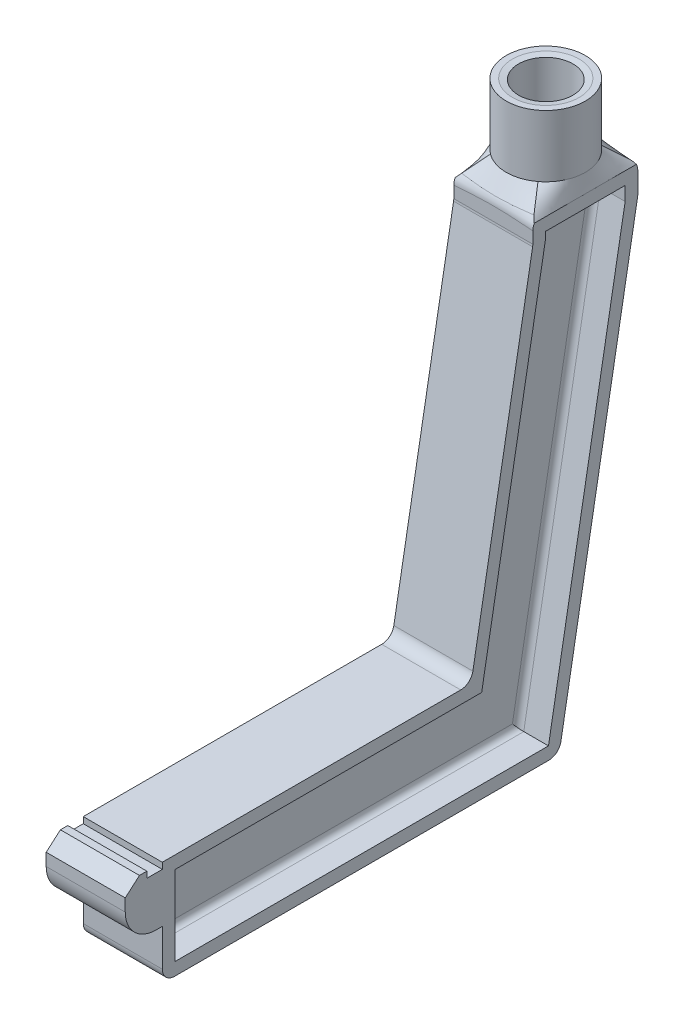
SolidWorks part; units mm, degrees
ref_plane "Front" through (0, 0, 0) normal (0, 0, 1) x (1, 0, 0)
ref_plane "Top" through (0, 0, 0) normal (0, 1, 0) x (1, 0, 0)
ref_plane "Right" through (0, 0, 0) normal (1, 0, 0) x (0, 0, -1)
sketch "Sketch1" plane through (0, 0, 0) normal (0, 1, 0) x (1, 0, 0)
  circle A0 centre (0, 0) radius 4.25 construction
  circle A1 centre (0, 0) radius 4.4
  circle A2 centre (0, 0) radius 6.4
  dimension "D1" = 8.5
  dimension "D3" = 2
  dimension "D2" = 0.15
extrude "Boss-Extrude1" add sketch "Sketch1" along normal blind 10
ref_plane "Plane1" through (0, -3, 0) normal (0, -1, 0) x (-1, 0, 0)
chamfer "Chamfer1" distance 1 angle 10 1 edges at (0, 10, 4.4) first distance on face at (0, 10, 6.4)
sketch "Sketch2" plane through (0, 0, 0) normal (0, -1, 0) x (1, 0, 0)
  circle A0 centre (0, 0) radius 6.4
  circle A1 centre (0, 0) radius 6.4 construction
sketch "Sketch3" plane through (0, -3, 0) normal (0, -1, 0) x (-1, 0, 0)
  line L1 (6.4, 8.5) -> (-6.4, 8.5)
  line L2 (6.4, 8.5) -> (6.4, -8.5)
  line L3 (6.4, -8.5) -> (-6.4, -8.5)
  line L4 (-6.4, 8.5) -> (-6.4, -8.5)
  line L5 (0, -8.5) -> (0, 8.5) construction
  line L6 (6.4, 0) -> (-6.4, 0) construction
  point P0 (0, 0)
  dimension "D1" = 17
  dimension "D2" = 12.8
loft "Loft1" add profiles "Sketch2", "Sketch3" connector at (0, 0, -6.4) connector at (-6.4, -3, -8.5)
sketch "Sketch4" plane through (0, 0, 0) normal (1, 0, 0) x (0, 0, -1)
  line L0 (-8.5, -3) -> (-8.5, -6)
  line L1 (8.5, -3) -> (8.5, -7.493)
  line L2 (8.5, -7.493) -> (-1.2357, -62.493)
  line L3 (-8.5, -6) -> (-18.5, -62.493)
  line L5 (-8.5, -3) -> (8.5, -3)
  line L7 (-1.2357, -62.493) -> (-4.2449, -79.493)
  line L8 (-4.2449, -79.493) -> (-68.5, -79.493)
  line L9 (-68.5, -79.493) -> (-68.5, -62.493)
  line L10 (-68.5, -62.493) -> (-18.5, -62.493)
  dimension "D1" = 3
  dimension "D2" = 17
  dimension "D3" = 10
  dimension "D4" = 55
  dimension "D5" = 17
  dimension "D6" = 60
extrude "Boss-Extrude2" add sketch "Sketch4" along normal mid plane 12.8 contours L10 L9 L8 L7 | L2 L1 L5 L0 L3 region at (0, -4.0854, 0)
sketch "Sketch5" plane through (0, 0, 0) normal (-1, 0, 0) x (0, 0, 1)
  line L8 (6.45, -5.05) -> (-6.45, -5.05)
  line L15 (6.45, -5.05) -> (-6.45, -5.05)
  line L17 (66.45, -64.543) -> (16.781, -64.543)
  line L21 (16.781, -64.543) -> (6.45, -6.18)
  line L22 (6.45, -6.18) -> (6.45, -5.05)
  line L24 (-6.45, -5.05) -> (-6.45, -7.313)
  line L25 (-6.45, -7.313) -> (5.9639, -77.443)
  line L26 (5.9639, -77.443) -> (66.45, -77.443)
  line L27 (66.45, -77.443) -> (66.45, -64.543)
  line L28 (66.45, -64.543) -> (16.781, -64.543)
  line L29 (16.781, -64.543) -> (6.45, -6.18)
  line L30 (6.45, -6.18) -> (6.45, -5.05)
  line L32 (-6.45, -5.05) -> (-6.45, -7.313)
  line L33 (-6.45, -7.313) -> (5.9639, -77.443)
  line L34 (5.9639, -77.443) -> (66.45, -77.443)
  line L35 (66.45, -77.443) -> (66.45, -64.543)
  dimension "D1" = 2.05
extrude "Cut-Extrude1" cut sketch "Sketch5" against normal blind 5 from surface starting at face at (-6.4, -37.4648, 21.0306)
extrude "Cut-Extrude2" cut sketch "Sketch5<2>" along normal blind 5 from surface starting at face at (6.4, -37.4648, 18.9056)
sketch "Sketch5<2>" plane through (0, 0, 0) normal (-1, 0, 0) x (0, 0, 1) same geometry as "Sketch5"
fillet "Fillet23" radius 1 16 edges at (-1.4, -5.615, 6.45) (-1.4, -35.3615, 11.6155) (-1.4, -64.543, 41.6155) (-1.4, -70.993, 66.45) (-1.4, -77.443, 36.207) (-1.4, -42.378, -0.243) (-1.4, -6.1815, -6.45) (-1.4, -5.05, 0) (1.4, -5.615, 6.45) (1.4, -5.05, 0) (1.4, -6.1815, -6.45) (1.4, -42.378, -0.243) (1.4, -77.443, 36.207) (1.4, -70.993, 66.45) (1.4, -64.543, 41.6155) (1.4, -35.3615, 11.6155)
sketch "Sketch6" plane through (0, 0, 0) normal (1, 0, 0) x (0, 0, -1)
  line L8 (-68.5, -63.493) -> (-71, -63.493)
  line L9 (-68.5, -79.493) -> (-68.5, -62.493) construction
  line L10 (-71, -63.493) -> (-71, -62.493)
  line L11 (-71, -62.493) -> (-72.2, -62.493)
  line L12 (-72.2, -62.493) -> (-74.5, -64.493)
  line L13 (-74.5, -64.493) -> (-74.5, -66.493)
  line L14 (-69.5, -71.493) -> (-68.5, -71.493)
  line L15 (-68.5, -71.493) -> (-68.5, -63.493)
  arc A0 (-74.5, -66.493) -> (-69.5, -71.493) centre (-69.5, -66.493) ccw
  dimension "D4" = 5
  dimension "D1" = 2
  dimension "D2" = 2.3
  dimension "D3" = 8
  dimension "D7" = 2.5
  dimension "D8" = 1
  dimension "D9" = 1.2
extrude "Boss-Extrude3" add sketch "Sketch6" along normal mid plane 12.8
fillet "Fillet30" radius 2 5 edges at (0, -62.493, 18.5) (0, -7.493, -8.5) (0, -79.493, 4.2449) (0, -79.493, 68.5) (0, -6, 8.5)
fillet "Fillet36" radius 2 1 edges
fillet "Fillet37" radius 2 1 edges
sketch "Sketch7" plane through (0, 0, 0) normal (1, 0, 0) x (0, 0, -1)
  line L0 (-66.45, -77.443) -> (-66.45, -64.543) construction
  line L1 (-66.45, -88.7612) -> (8.5, -88.7612)
  line L2 (-66.45, -88.7612) -> (-66.45, 10)
  line L3 (-66.45, 10) -> (8.5, 10)
  line L4 (8.5, -88.7612) -> (8.5, 10)
  line L5 (8.5, -3.9405) -> (8.5, -7.3174) construction
  line L6 (5.4, 10) -> (-5.4, 10) construction
extrude "Cut-Extrude3" [suppressed] cut sketch "Sketch7" against normal through all both and the other way through all
